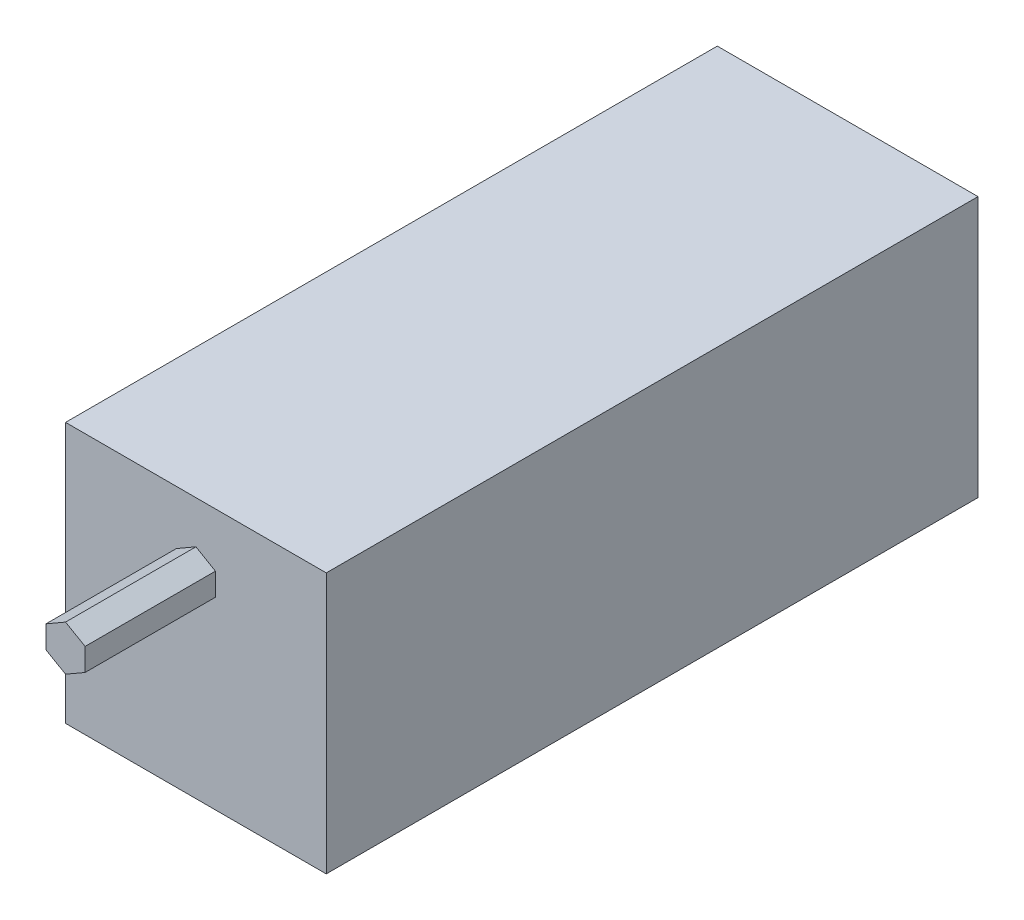
SolidWorks part; units mm, degrees
ref_plane "Plan de face" through (0, 0, 0) normal (0, 0, 1) x (1, 0, 0)
ref_plane "Plan de dessus" through (0, 0, 0) normal (0, 1, 0) x (1, 0, 0)
ref_plane "Plan de droite" through (0, 0, 0) normal (1, 0, 0) x (0, 0, -1)
sketch "Esquisse1" plane through (0, 0, 0) normal (0, 1, 0) x (1, 0, 0)
  line L1 (0, 0) -> (40, 0)
  line L2 (0, 0) -> (0, 100)
  line L3 (0, 100) -> (40, 100)
  line L4 (40, 0) -> (40, 100)
  dimension "D1" = 40
  dimension "D2" = 100
extrude "Boss.-Extru.1" add sketch "Esquisse1" along normal blind 40
sketch "Esquisse2" plane through (0, 0, 0) normal (0, 0, 1) x (1, 0, 0)
  line L0 (0, 40) -> (40, 40) construction
  line L1 (23, 28.2679) -> (23, 31.7321)
  line L2 (23, 31.7321) -> (20, 33.4641)
  line L3 (20, 33.4641) -> (17, 31.7321)
  line L4 (17, 31.7321) -> (17, 28.2679)
  line L5 (17, 28.2679) -> (20, 26.5359)
  line L6 (20, 26.5359) -> (23, 28.2679)
  line L8 (20, 40) -> (20, 0) construction
  line L9 (0, 0) -> (40, 0) construction
  circle A0 centre (20, 30) radius 3 construction
  point P14 (0, 0)
  point P15 (0, 0)
  dimension "D1" = 6
  dimension "D2" = 10
extrude "Boss.-Extru.2" add sketch "Esquisse2" along normal blind 20
ref_axis "Axe1" through (20, 30, -135.662) along (0, 0, 1)
